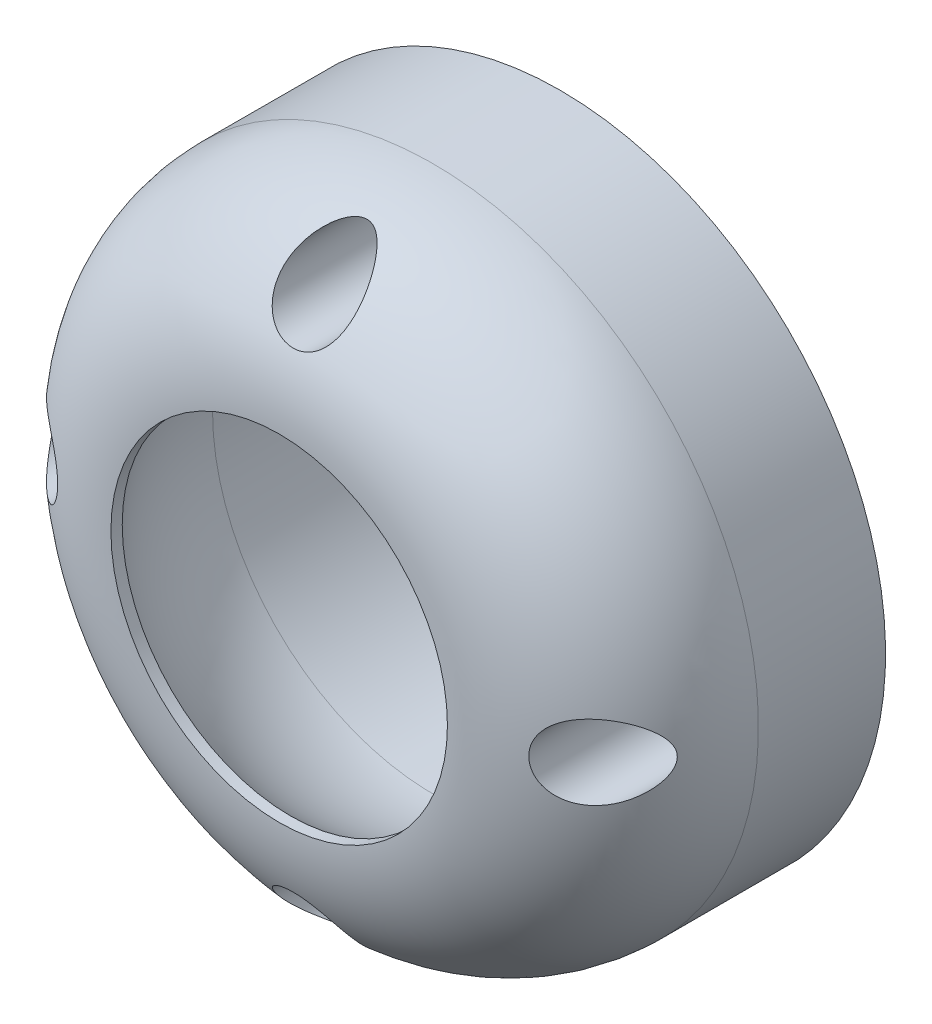
SolidWorks part; units mm, degrees
ref_plane "正面" through (0, 0, 0) normal (0, 0, 1) x (1, 0, 0)
ref_plane "平面" through (0, 0, 0) normal (0, 1, 0) x (1, 0, 0)
ref_plane "右側面" through (0, 0, 0) normal (1, 0, 0) x (0, 0, -1)
sketch "ｽｹｯﾁ1" plane through (0, 0, 0) normal (0, 0, 1) x (1, 0, 0)
  line L0 (-15.25, 0) -> (-14.75, 0)
  line L1 (14.75, 0) -> (15.25, 0)
  line L2 (14.75, 0) -> (-14.75, 0) construction
  arc A0 (14.75, 0) -> (-14.75, 0) centre (0, 0) cw
  arc A1 (-15.25, 0) -> (15.25, 0) centre (0, 0) ccw
  dimension "D2" = 14.75
  dimension "D1" = 15.25
revolve "回転1" add sketch "ｽｹｯﾁ1" angle 180 about L2
sketch "ｽｹｯﾁ2" plane through (0, 0, 0) normal (0, 0, -1) x (-1, 0, 0)
  circle A0 centre (0, 0) radius 11.25
  dimension "D1" = 22.5
extrude "ｶｯﾄ - 押し出し1" cut sketch "ｽｹｯﾁ2" against normal through all
sketch "ｽｹｯﾁ4" plane through (0, 0, 0) normal (1, 0, 0) x (0, 0, -1)
  line L0 (0, 15.25) -> (0, 21.75)
  line L1 (0, 0) -> (0, 15.25) construction
  line L2 (0, 0) -> (-17.7206, 0) construction
  arc A0 (-10.2956, 11.25) -> (0, 21.75) centre (0, 11.4524) cw
  arc A1 (0, 15.25) -> (-10.2956, 11.25) centre (0, 0) ccw
  arc A2 (0, 15.25) -> (-10.2956, 11.25) centre (0, 0) ccw construction
  dimension "D1" = 6.5
revolve "回転2" add sketch "ｽｹｯﾁ4" angle 360 about L2
sketch "ｽｹｯﾁ3" plane through (0, 0, 0) normal (0, 0, -1) x (-1, 0, 0)
  circle A0 centre (0, 0) radius 14.75
  circle A1 centre (0, 0) radius 21.75
  circle A2 centre (0, 0) radius 14.75 construction
  circle A4 centre (0, 0) radius 21.75 construction
  dimension "D1" = 7
extrude "ﾎﾞｽ - 押し出し1" add sketch "ｽｹｯﾁ3" along normal blind 8.5
sketch "ｽｹｯﾁ7" plane through (0, 0, -8.5) normal (0, 0, -1) x (-1, 0, 0)
  line L0 (0, -14.75) -> (0, 0) construction
  line L1 (0, -14.75) -> (0, -18.25) construction
  line L2 (0, -18.25) -> (0, -21.75) construction
  circle A0 centre (0, 0) radius 18.25 construction
  circle A3 centre (0, -18.25) radius 1.1
  circle A4 centre (-18.25, 0) radius 1.1
  circle A5 centre (0, 18.25) radius 1.1
  circle A6 centre (18.25, 0) radius 1.1
  circle A8 centre (0, 0) radius 21.75 construction
  circle A9 centre (0, 0) radius 14.75 construction
  point P23 (0, 0)
  dimension "D2" = 2.2
  dimension "D1" = 4
extrude "ｶｯﾄ - 押し出し2" cut sketch "ｽｹｯﾁ7" against normal through all
ref_plane "平面1" through (0, 0, 0) normal (0, 0, 1) x (1, 0, 0)
sketch "ｽｹｯﾁ8" plane through (0, 0, 0) normal (0, 0, 1) x (1, 0, 0)
  line L0 (0, 0) -> (0, 14.75) construction
  line L1 (0, 14.75) -> (0, 18.25) construction
  line L2 (0, 18.25) -> (0, 21.75) construction
  circle A0 centre (0, 0) radius 18.25 construction
  circle A2 centre (0, 18.25) radius 2.5
  circle A3 centre (0, 18.25) radius 1.1 construction
  circle A4 centre (18.25, 0) radius 2.5
  circle A5 centre (0, -18.25) radius 2.5
  circle A6 centre (-18.25, 0) radius 2.5
  circle A7 centre (0, 0) radius 21.75 construction
  point P21 (0, 0)
  point P24 (0, 0)
  dimension "D1" = 5
  dimension "D3" = 3.5
  dimension "D2" = 4
extrude "ｶｯﾄ - 押し出し7" cut sketch "ｽｹｯﾁ8" along normal through all from offset 6.5 offset against normal yes
